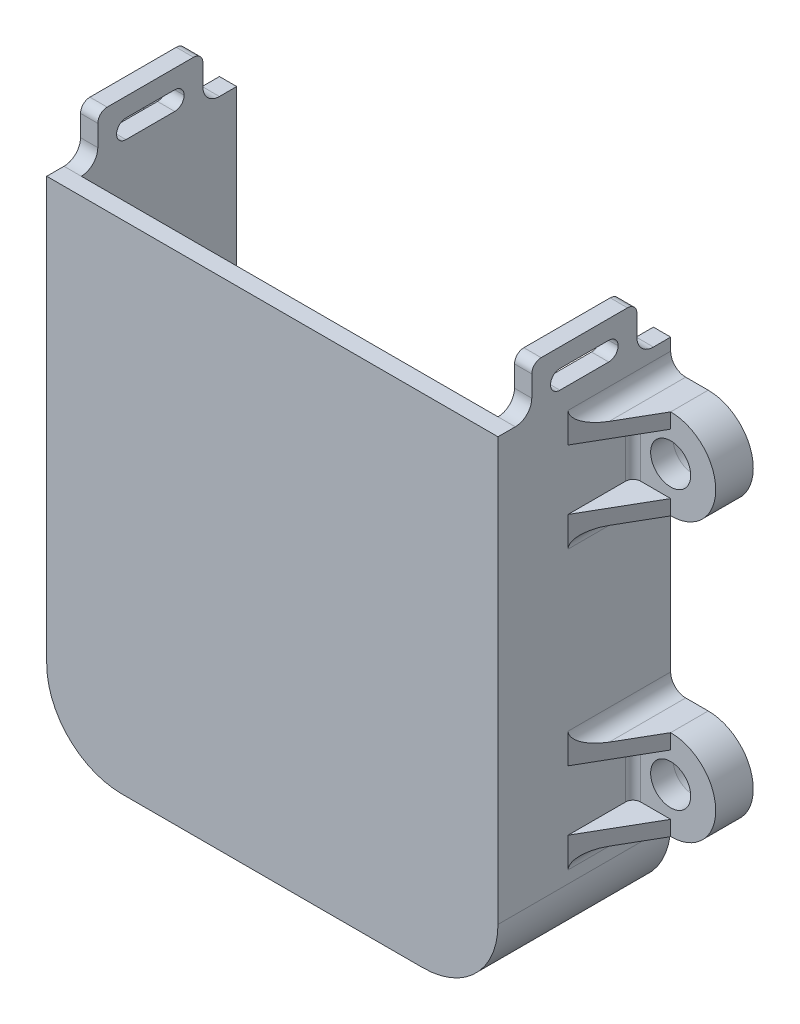
SolidWorks part; units mm, degrees
ref_plane "Front Plane" through (0, 0, 0) normal (0, 0, 1) x (1, 0, 0)
ref_plane "Top Plane" through (0, 0, 0) normal (0, 1, 0) x (1, 0, 0)
ref_plane "Right Plane" through (0, 0, 0) normal (1, 0, 0) x (0, 0, -1)
sketch "Sketch1" plane through (0, 0, 0) normal (0, 0, 1) x (1, 0, 0)
  line L0 (0, 0) -> (50.927, 0)
  line L1 (63.627, 12.7) -> (63.627, 84.1375)
  line L3 (-12.7, 84.1375) -> (-12.7, 12.7)
  line L4 (-12.7, 84.1375) -> (63.627, 84.1375)
  arc A0 (50.927, 0) -> (63.627, 12.7) centre (50.927, 12.7) ccw
  arc A3 (-12.7, 12.7) -> (0, 0) centre (0, 12.7) ccw
  dimension "D2" = 12.7
  dimension "D4" = 12.7
  dimension "D1" = 50.927
  dimension "D3" = 71.4375
  dimension "D6" = 71.4375
extrude "Boss-Extrude1" add sketch "Sketch1" against normal blind 29.21
shell "Shell1" thickness 2.921
sketch "Sketch3" plane through (0, 0, 0) normal (0, -1, 0) x (-1, 0, 0)
  line L0 (0, 0) -> (-50.927, 0) construction
  line L1 (-42.3545, 3.175) -> (7.9375, 3.175)
  line L2 (-42.3545, 3.175) -> (-42.3545, 19.3675)
  line L3 (-42.3545, 19.3675) -> (7.9375, 19.3675)
  line L4 (7.9375, 3.175) -> (7.9375, 19.3675)
  line L5 (12.7, 29.21) -> (12.7, 0) construction
  dimension "D1" = 16.1925
  dimension "D2" = 3.175
  dimension "D3" = 4.7625
  dimension "D4" = 50.292
extrude "Cut-Extrude2" cut sketch "Sketch3" against normal blind 26.9875
sketch "Sketch4" plane through (0, 0, -29.21) normal (0, 0, -1) x (-1, 0, 0)
  line L0 (12.7, 84.1375) -> (12.7, 12.7) construction
  line L1 (12.7, 17.3038) -> (19.05, 17.3038)
  line L2 (12.7, 17.3038) -> (12.7, 32.5437)
  line L3 (12.7, 32.5437) -> (19.05, 32.5437)
  line L5 (-63.627, 12.7) -> (-63.627, 84.1375) construction
  line L6 (12.7, 79.5338) -> (19.05, 79.5338)
  line L7 (12.7, 79.5338) -> (12.7, 64.2938)
  line L8 (12.7, 64.2938) -> (19.05, 64.2938)
  line L10 (-63.627, 79.5337) -> (-69.977, 79.5337)
  line L11 (-63.627, 79.5337) -> (-63.627, 64.2937)
  line L12 (-63.627, 64.2937) -> (-69.977, 64.2937)
  line L15 (-63.627, 32.5437) -> (-69.977, 32.5437)
  line L16 (-63.627, 32.5437) -> (-63.627, 17.3037)
  line L17 (-63.627, 17.3037) -> (-69.977, 17.3037)
  line L19 (9.779, 48.4187) -> (-60.706, 48.4187) construction
  line L20 (9.779, 84.1375) -> (9.779, 12.7) construction
  line L21 (-60.706, 12.7) -> (-60.706, 84.1375) construction
  arc A0 (-69.977, 64.2937) -> (-69.977, 79.5337) centre (-69.977, 71.9137) cw
  arc A1 (-69.977, 32.5437) -> (-69.977, 17.3037) centre (-69.977, 24.9237) ccw
  arc A2 (19.05, 17.3038) -> (19.05, 32.5437) centre (19.05, 24.9237) ccw
  arc A3 (19.05, 64.2938) -> (19.05, 79.5338) centre (19.05, 71.9138) ccw
  point P24 (15.875, 32.5437)
  dimension "D1" = 15.24
  dimension "D2" = 6.35
  dimension "D3" = 15.24
  dimension "D4" = 6.35
  dimension "D5" = 15.24
  dimension "D6" = 6.35
  dimension "D7" = 15.24
  dimension "D8" = 6.35
  dimension "D9" = 31.75
  dimension "D10" = 31.75
  dimension "D11" = 15.875
  dimension "D12" = 15.875
extrude "Boss-Extrude2" add sketch "Sketch4" against normal blind 6.35
fillet "Fillet3" radius 1.27 4 edges at (-12.7, 24.9237, -22.86) (-12.7, 71.9138, -22.86) (63.627, 71.9137, -22.86) (63.627, 24.9237, -22.86)
fillet "Fillet4" radius 1.27 4 edges at (42.3545, 1.4605, -3.175) (42.3545, 1.4605, -19.3675) (-7.9375, 4.8871, -19.3675) (-7.9375, 4.8871, -3.175)
sketch "Sketch6" plane through (0, 79.5337, 0) normal (0, 1, 0) x (1, 0, 0)
  line L0 (69.977, 22.86) -> (63.627, 11.8615)
  line L3 (63.627, 29.21) -> (63.627, 0) construction
  dimension "D1" = 12.7
rib "Rib1" sketch "Sketch6" sketch "Sketch6" thickness 2.54 extrusion direction parallel to sketch draft on no parameters "D1"=2.54
ref_plane "Plane1" through (0, 71.9137, 0) normal (0, 1, 0) x (1, 0, 0)
mirror "Mirror1" about plane through (0, 71.9137, 0) normal (0, 1, 0) of "Rib1"
ref_plane "Plane2" through (0, 48.4187, 0) normal (0, -1, 0) x (-1, 0, 0)
mirror "Mirror2" about plane through (0, 48.4187, 0) normal (0, -1, 0) of "Mirror1", "Rib1"
ref_plane "Plane3" through (25.4635, 0, 0) normal (1, 0, 0) x (0, 0, -1)
mirror "Mirror3" about plane through (25.4635, 0, 0) normal (1, 0, 0) of "Mirror2", "Rib1", "Mirror1"
fillet "Fillet6" radius 2.54 8 edges at (-12.7, 64.2938, -20.5357) (-12.7, 79.5337, -20.5357) (-12.7, 32.5437, -20.5357) (-12.7, 17.3037, -20.5357) (63.627, 17.3037, -20.5357) (63.627, 32.5437, -20.5357) (63.627, 79.5337, -20.5357) (63.627, 64.2937, -20.5357)
sketch "Sketch7" plane through (0, 0, -22.86) normal (0, 0, 1) x (1, 0, 0)
  circle A0 centre (69.977, 71.9137) radius 3.3909
  dimension "D1" = 6.7818
extrude "Cut-Extrude3" cut sketch "Sketch7" against normal blind 6.35 contours A0
mirror "Mirror4" about plane through (25.4635, 0, 0) normal (1, 0, 0) of "Cut-Extrude3" second plane through (0, 48.4187, 0) second plane normal (0, -1, 0)
chamfer "Chamfer1" distance 2.54 angle 8 4 edges at (73.3679, 71.9137, -29.21) (73.3679, 24.9237, -29.21) (-22.4409, 71.9137, -29.21) (-22.4409, 24.9237, -29.21)
sketch "Sketch10" plane through (63.627, 0, 0) normal (1, 0, 0) x (0, 0, -1)
  line L0 (29.21, 84.1375) -> (0, 84.1375) construction
  line L1 (5.715, 84.1375) -> (23.495, 84.1375)
  line L2 (5.715, 84.1375) -> (5.715, 92.075)
  line L3 (5.715, 92.075) -> (23.495, 92.075)
  line L4 (23.495, 84.1375) -> (23.495, 92.075)
  line L5 (14.605, 84.1375) -> (14.605, 75.9932) construction
  line L6 (14.605, 92.075) -> (14.605, 84.1375) construction
  dimension "D1" = 17.78
  dimension "D2" = 7.9375
extrude "Boss-Extrude3" add sketch "Sketch10" along direction (1, 0, 0) on the side against the normal blind 2.921
sketch "Sketch11" plane through (63.627, 0, 0) normal (1, 0, 0) x (0, 0, -1)
  line L0 (23.495, 92.075) -> (5.715, 92.075) construction
  line L1 (8.89, 88.9) -> (20.32, 88.9)
  line L2 (8.89, 88.9) -> (8.89, 85.725)
  line L3 (8.89, 85.725) -> (20.32, 85.725)
  line L4 (20.32, 88.9) -> (20.32, 85.725)
  line L5 (23.495, 84.1375) -> (23.495, 92.075) construction
  line L7 (5.715, 92.075) -> (5.715, 84.1375) construction
  dimension "D1" = 3.175
  dimension "D2" = 3.175
  dimension "D3" = 3.175
  dimension "D4" = 3.175
extrude "Cut-Extrude4" cut sketch "Sketch11" against normal blind 2.921
ref_plane "Plane4" through (25.4635, 0, 0) normal (1, 0, 0) x (0, 0, -1)
fillet "Fillet7" radius 1.5875 6 edges at (62.1665, 85.725, -8.89) (62.1665, 88.9, -8.89) (62.1665, 88.9, -20.32) (62.1665, 85.725, -20.32) (62.1665, 92.075, -23.495) (62.1665, 92.075, -5.715)
mirror "Mirror5" about plane through (25.4635, 0, 0) normal (1, 0, 0) of "Fillet7", "Cut-Extrude4", "Boss-Extrude3"
fillet "Fillet8" radius 2.794 4 edges at (-11.2395, 84.1375, -5.715) (-11.2395, 84.1375, -23.495) (62.1665, 84.1375, -23.495) (62.1665, 84.1375, -5.715)
